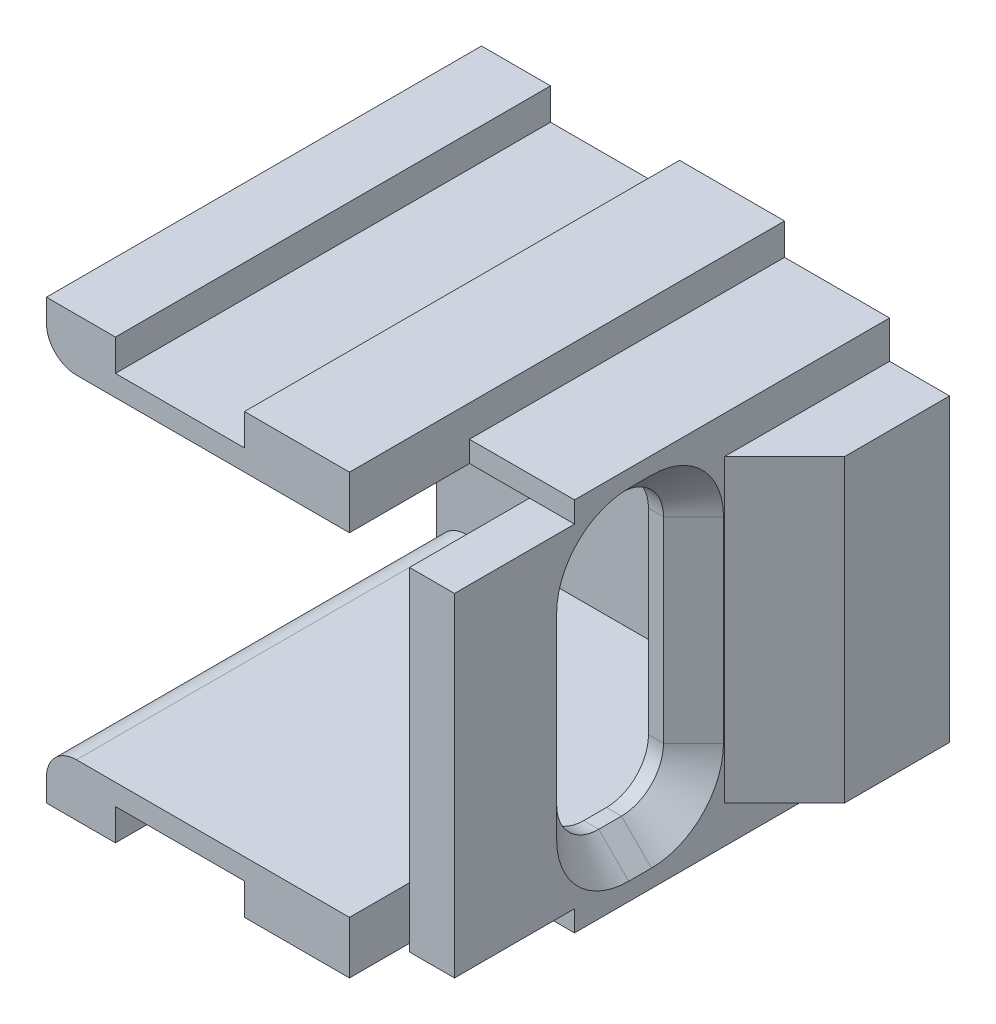
SolidWorks part; units mm, degrees
ref_plane "Front Plane" through (0, 0, 0) normal (1, 0, 0) x (0, 1, 0)
ref_plane "Top Plane" through (0, 0, 0) normal (0, 0, 1) x (0, 1, 0)
ref_plane "Right Plane" through (0, 0, 0) normal (0, 1, 0) x (-1, 0, 0)
sketch "Sketch2" plane through (0, 0, 0) normal (1, 0, 0) x (0, 1, 0)
  line L1 (5, 5.25) -> (-5, 5.25)
  line L2 (5, 5.25) -> (5, -5.25)
  line L3 (5, -5.25) -> (-5, -5.25)
  line L4 (-5, 5.25) -> (-5, -5.25)
  line L5 (5, 5.25) -> (-5, -5.25) construction
  line L6 (5, -5.25) -> (-5, 5.25) construction
  point P0 (0, 0)
  dimension "D1" = 10.5
  dimension "D2" = 10
extrude "Boss-Extrude1" add sketch "Sketch2" along normal blind 2
sketch "Sketch3" plane through (0, 0, 0) normal (-1, 0, 0) x (0, -1, 0)
  line L1 (-6.25, -5.25) -> (6.25, -5.25)
  line L2 (-6.25, -5.25) -> (-6.25, 9.25)
  line L3 (-6.25, 9.25) -> (6.25, 9.25)
  line L4 (5, -5.25) -> (5, 5.25)
  line L5 (5, 5.25) -> (-5, 5.25)
  line L6 (-5, 5.25) -> (-5, -5.25)
  line L7 (-5, -5.25) -> (5, -5.25)
  line L8 (5, -5.25) -> (5, 5.25) construction
  line L9 (5, 5.25) -> (-5, 5.25) construction
  line L10 (-5, 5.25) -> (-5, -5.25) construction
  line L11 (-5, -5.25) -> (5, -5.25) construction
  line L12 (6.25, -5.25) -> (6.25, 9.25)
  point P8 (0, -5.25)
  point P9 (0, -5.25)
  dimension "D2" = 12.5
  dimension "D3" = 14.5
  dimension "D1" = 0
extrude "Boss-Extrude2" add sketch "Sketch3" along normal blind 3.5
sketch "Sketch4" plane through (-3.5, 0, 0) normal (-1, 0, 0) x (0, -1, 0)
  line L1 (-7.3, -5.25) -> (7.3, -5.25)
  line L2 (-7.3, -5.25) -> (-7.3, 9.25)
  line L3 (-7.3, 9.25) -> (7.3, 9.25)
  line L4 (-6.25, 9.25) -> (-6.25, -5.25)
  line L5 (-6.25, -5.25) -> (6.25, -5.25)
  line L6 (6.25, -5.25) -> (6.25, 9.25)
  line L7 (6.25, 9.25) -> (-6.25, 9.25)
  line L8 (-6.25, 9.25) -> (-6.25, -5.25) construction
  line L9 (-6.25, -5.25) -> (6.25, -5.25) construction
  line L10 (6.25, -5.25) -> (6.25, 9.25) construction
  line L11 (6.25, 9.25) -> (-6.25, 9.25) construction
  line L12 (7.3, -5.25) -> (7.3, 9.25)
  point P9 (0, -5.25)
  point P10 (0, -5.25)
  dimension "D2" = 14.6
  dimension "D1" = 0
extrude "Boss-Extrude3" add sketch "Sketch4" along normal blind 3.5
sketch "Sketch5" plane through (-7, 0, 0) normal (-1, 0, 0) x (0, -1, 0)
  line L1 (-6.25, -5.25) -> (6.25, -5.25)
  line L2 (-6.25, -5.25) -> (-6.25, 9.25)
  line L3 (-6.25, 9.25) -> (6.25, 9.25)
  line L4 (-7.3, 9.25) -> (-7.3, -5.25)
  line L5 (-7.3, -5.25) -> (7.3, -5.25)
  line L6 (7.3, -5.25) -> (7.3, 9.25)
  line L7 (7.3, 9.25) -> (-7.3, 9.25)
  line L8 (-7.3, 9.25) -> (-7.3, -5.25) construction
  line L9 (-7.3, -5.25) -> (7.3, -5.25) construction
  line L10 (7.3, -5.25) -> (7.3, 9.25) construction
  line L11 (7.3, 9.25) -> (-7.3, 9.25) construction
  line L12 (6.25, -5.25) -> (6.25, 9.25)
  point P8 (0, -5.25)
  point P9 (0, -5.25)
  dimension "D2" = 12.5
  dimension "D1" = 0
extrude "Boss-Extrude4" add sketch "Sketch5" along normal blind 4.3
sketch "Sketch6" plane through (-11.3, 0, 0) normal (-1, 0, 0) x (0, -1, 0)
  line L0 (6.25, 9.25) -> (6.25, -5.25) construction
  line L1 (6.25, -5.25) -> (7.3, -5.25) construction
  line L2 (7.3, -5.25) -> (7.3, 9.25) construction
  line L3 (7.3, 9.25) -> (6.25, 9.25) construction
  line L4 (-6.25, 9.25) -> (-6.25, -5.25) construction
  line L5 (-6.25, -5.25) -> (6.25, -5.25) construction
  line L6 (6.25, -5.25) -> (6.25, 9.25) construction
  line L7 (6.25, 9.25) -> (-6.25, 9.25) construction
  line L8 (-6.25, -5.25) -> (-6.25, 9.25) construction
  line L9 (-6.25, 9.25) -> (-7.3, 9.25) construction
  line L10 (-7.3, 9.25) -> (-7.3, -5.25) construction
  line L11 (-7.3, -5.25) -> (-6.25, -5.25) construction
  line L12 (6.25, 9.25) -> (6.25, -5.25) construction
  line L13 (6.25, -5.25) -> (7.3, -5.25)
  line L14 (7.3, -5.25) -> (7.3, 9.25)
  line L15 (7.3, 9.25) -> (6.25, 9.25)
  line L16 (-6.25, 9.25) -> (-6.25, -5.25) construction
  line L17 (-6.25, -5.25) -> (6.25, -5.25)
  line L18 (6.25, -5.25) -> (6.25, 9.25) construction
  line L19 (6.25, 9.25) -> (-6.25, 9.25)
  line L20 (-6.25, -5.25) -> (-6.25, 9.25) construction
  line L21 (-6.25, 9.25) -> (-7.3, 9.25)
  line L22 (-7.3, 9.25) -> (-7.3, -5.25)
  line L23 (-7.3, -5.25) -> (-6.25, -5.25)
extrude "Boss-Extrude5" add sketch "Sketch6" along normal blind 2.3
sketch "Sketch8" plane through (0, 0, 9.25) normal (0, 0, 1) x (1, 0, 0)
  line L1 (-13.6, 5.55) -> (-1.5, 5.55)
  line L2 (-13.6, 5.55) -> (-13.6, -5.55)
  line L3 (-13.6, -5.55) -> (-1.5, -5.55)
  line L4 (-1.5, 5.55) -> (-1.5, -5.55)
  line L16 (0, -6.25) -> (0, 6.25)
  line L17 (0, 6.25) -> (-3.5, 6.25)
  line L18 (-3.5, 6.25) -> (-3.5, 7.3)
  line L19 (-3.5, 7.3) -> (-7, 7.3)
  line L20 (-7, 7.3) -> (-7, 6.25)
  line L21 (-7, 6.25) -> (-11.3, 6.25)
  line L22 (-11.3, 6.25) -> (-11.3, 7.3)
  line L23 (-11.3, 7.3) -> (-13.6, 7.3)
  line L24 (-13.6, 7.3) -> (-13.6, -7.3)
  line L25 (-13.6, -7.3) -> (-11.3, -7.3)
  line L26 (-11.3, -7.3) -> (-11.3, -6.25)
  line L27 (-11.3, -6.25) -> (-7, -6.25)
  line L28 (-7, -6.25) -> (-7, -7.3)
  line L29 (-7, -7.3) -> (-3.5, -7.3)
  line L30 (-3.5, -7.3) -> (-3.5, -6.25)
  line L31 (-3.5, -6.25) -> (0, -6.25)
  line L32 (0, -6.25) -> (0, 6.25) construction
  line L33 (0, 6.25) -> (-3.5, 6.25) construction
  line L34 (-3.5, 6.25) -> (-3.5, 7.3) construction
  line L35 (-3.5, 7.3) -> (-7, 7.3) construction
  line L36 (-7, 7.3) -> (-7, 6.25) construction
  line L37 (-7, 6.25) -> (-11.3, 6.25) construction
  line L38 (-11.3, 6.25) -> (-11.3, 7.3) construction
  line L39 (-11.3, 7.3) -> (-13.6, 7.3) construction
  line L40 (-13.6, 7.3) -> (-13.6, -7.3) construction
  line L41 (-13.6, -7.3) -> (-11.3, -7.3) construction
  line L42 (-11.3, -7.3) -> (-11.3, -6.25) construction
  line L43 (-11.3, -6.25) -> (-7, -6.25) construction
  line L44 (-7, -6.25) -> (-7, -7.3) construction
  line L45 (-7, -7.3) -> (-3.5, -7.3) construction
  line L46 (-3.5, -7.3) -> (-3.5, -6.25) construction
  line L47 (-3.5, -6.25) -> (0, -6.25) construction
  point P10 (-13.6, 0)
  point P12 (-13.6, 0)
  dimension "D2" = 0.7
  dimension "D3" = 1.5
  dimension "D1" = 0
extrude "Cut-Extrude1" cut sketch "Sketch8" against normal blind 13
sketch "Sketch10" plane through (0, 0, 9.25) normal (0, 0, 1) x (1, 0, 0)
  line L0 (-1.5, 5.55) -> (-13.6, 5.55) construction
  line L9 (0, 6.25) -> (-3.5, 6.25)
  line L10 (0, 6.25) -> (0, 5.55)
  line L11 (0, 5.55) -> (-3.5, 5.55)
  line L12 (-3.5, 6.25) -> (-3.5, 5.55)
  line L13 (-13.6, -5.55) -> (-1.5, -5.55) construction
  line L14 (0, -6.25) -> (-3.5, -6.25)
  line L15 (0, -6.25) -> (0, -5.55)
  line L16 (0, -5.55) -> (-3.5, -5.55)
  line L17 (-3.5, -6.25) -> (-3.5, -5.55)
extrude "Cut-Extrude6" cut sketch "Sketch10" against normal up to surface (4 mm away) up to face at (1, 0, 5.25)
fillet "Fillet1" radius 1 2 edges at (-13.6, -5.55, 2.75) (-13.6, 5.55, 2.75)
sketch "Sketch11" plane through (0, 0, 0) normal (1, 0, 0) x (0, 0, -1)
  line L0 (-1.485, -3.18) -> (-1.485, 0.01) construction
  line L1 (-1.485, 3.2) -> (-1.485, 0.01) construction
  line L2 (-3.365, 4.48) -> (-2.765, 4.48) construction
  line L3 (-4.645, 0.01) -> (-4.645, 3.2) construction
  line L4 (-4.645, 0.01) -> (-4.645, -3.18) construction
  line L5 (-3.365, -4.46) -> (-2.765, -4.46) construction
  line L6 (-1.485, -3.18) -> (-1.485, 0.01) construction
  line L7 (-1.485, 3.2) -> (-1.485, 0.01) construction
  line L8 (-3.365, 4.48) -> (-2.765, 4.48) construction
  line L9 (-4.645, 0.01) -> (-4.645, 3.2) construction
  line L10 (-4.645, 0.01) -> (-4.645, -3.18) construction
  line L11 (-3.365, -4.46) -> (-2.765, -4.46) construction
  line L18 (-3.365, 3.2) -> (-2.765, -3.18) construction
  line L20 (-4.845, 4.68) -> (-1.285, 4.68)
  line L21 (-4.845, 4.68) -> (-4.845, -4.66)
  line L22 (-4.845, -4.66) -> (-1.285, -4.66)
  line L23 (-1.285, 4.68) -> (-1.285, -4.66)
  line L24 (-4.845, 4.68) -> (-1.285, -4.66) construction
  line L25 (-4.845, -4.66) -> (-1.285, 4.68) construction
  arc A0 (-1.485, 3.2) -> (-2.765, 4.48) centre (-2.765, 3.2) ccw construction
  arc A1 (-3.365, 4.48) -> (-4.645, 3.2) centre (-3.365, 3.2) ccw construction
  arc A2 (-4.645, -3.18) -> (-3.365, -4.46) centre (-3.365, -3.18) ccw construction
  arc A3 (-2.765, -4.46) -> (-1.485, -3.18) centre (-2.765, -3.18) ccw construction
  arc A4 (-1.485, 3.2) -> (-2.765, 4.48) centre (-2.765, 3.2) ccw construction
  arc A5 (-3.365, 4.48) -> (-4.645, 3.2) centre (-3.365, 3.2) ccw construction
  arc A6 (-4.645, -3.18) -> (-3.365, -4.46) centre (-3.365, -3.18) ccw construction
  arc A7 (-2.765, -4.46) -> (-1.485, -3.18) centre (-2.765, -3.18) ccw construction
  point P14 (-3.065, 0.01)
  point P15 (-3.065, 0.01)
  dimension "D1" = 0.2
  dimension "D2" = 0.2
sketch "Sketch12" plane through (0, 0, 5.25) normal (0, 0, 1) x (1, 0, 0)
  line L4 (0, 5) -> (0, -5)
  line L5 (0, -5) -> (2, -5)
  line L6 (2, -5) -> (2, 5)
  line L7 (2, 5) -> (0, 5)
  line L8 (0, 5) -> (0, -5)
  line L9 (0, -5) -> (2, -5)
  line L10 (2, -5) -> (2, 5)
  line L11 (2, 5) -> (0, 5)
  dimension "D1" = 0
extrude "Cut-Extrude8" cut sketch "Sketch12" against normal blind 5
extrude "Cut-Extrude9" cut sketch "Sketch11" against normal up to surface (1.5 mm away) up to face at (-1.5, 0, 3.5833)
fillet "Fillet2" radius 1.4 4 edges at (-0.75, -4.66, 4.845) (-0.75, 4.68, 4.845) (-0.75, -4.66, 1.285) (-0.75, 4.68, 1.285)
chamfer "Chamfer1" distance 1 angle 45 8 edges at (0, 4.27, 1.6951) (0, 0.01, 1.285) (0, 4.68, 3.065) (0, -4.2499, 1.6951) (0, 4.27, 4.4349) (0, -4.66, 3.065) (0, 0.01, 4.845) (0, -4.2499, 4.4349)
chamfer "Chamfer2" distance 2 angle 45 1 edges at (2, 0, 0.25)
